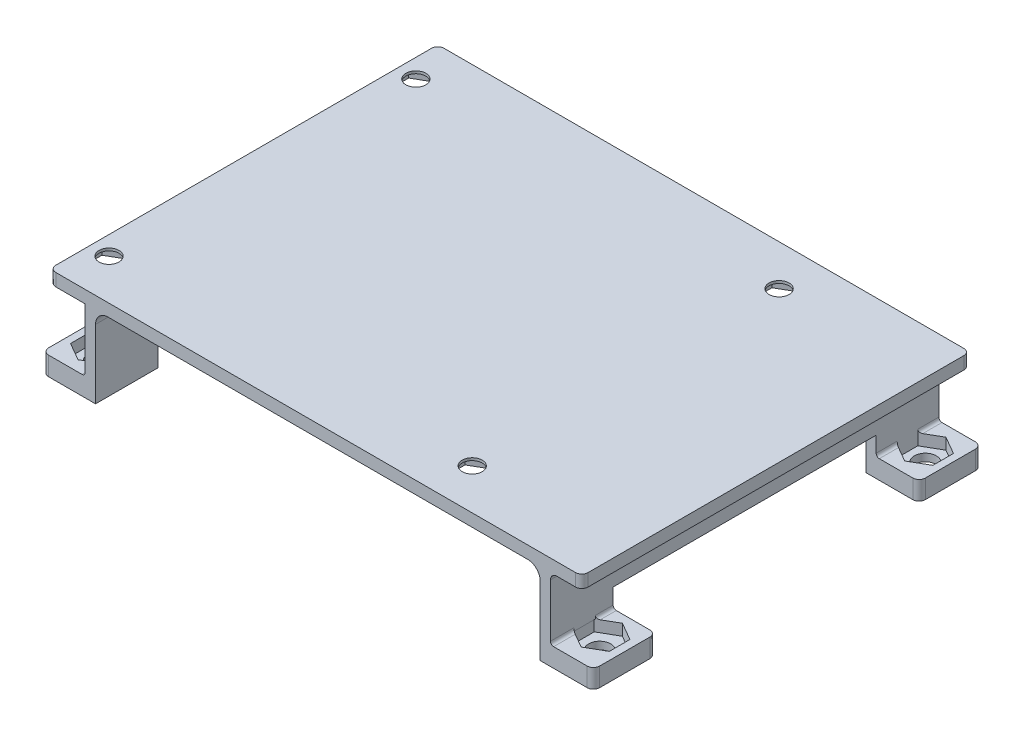
SolidWorks part; units mm, degrees
ref_plane "前基準面" through (0, 0, 0) normal (0, 0, 1) x (1, 0, 0)
ref_plane "上基準面" through (0, 0, 0) normal (0, 1, 0) x (1, 0, 0)
ref_plane "右基準面" through (0, 0, 0) normal (1, 0, 0) x (0, 0, -1)
sketch "草圖1" plane through (0, 0, 0) normal (0, 0, 1) x (1, 0, 0)
  line L0 (-133.4262, 0) -> (6537.8852, 0) construction
  line L1 (0, -133.4262) -> (0, 6537.8852) construction
  line L2 (-44, 0) -> (-44, 3)
  line L3 (-44, 3) -> (-37.15, 3)
  line L4 (-37.15, 3) -> (-37.15, 13)
  line L6 (37.15, 13) -> (37.15, 3)
  line L7 (37.15, 3) -> (44, 3)
  line L8 (44, 3) -> (44, 0)
  line L10 (-35.5, 0) -> (-35.5, 13)
  line L11 (-35.5, 13) -> (35.5, 13)
  line L12 (35.5, 13) -> (35.5, 0)
  line L13 (-44, 0) -> (-35.5, 0)
  line L14 (35.5, 0) -> (44, 0)
  line L16 (-42.85, 15) -> (-42.85, 13)
  line L17 (-37.15, 13) -> (-42.85, 13)
  line L18 (-42.85, 15) -> (42.15, 15)
  line L19 (42.15, 15) -> (42.15, 13)
  line L20 (42.15, 13) -> (37.15, 13)
  dimension "D1" = 1.65
  dimension "D2" = 13
  dimension "D3" = 71
  dimension "D4" = 88
  dimension "D5" = 2
  dimension "D6" = 3
  dimension "D7" = 85
  dimension "D8" = 5.7
extrude "填料-伸長1" add sketch "草圖1" along normal mid plane 62
sketch "草圖2" plane through (0, 0, 0) normal (1, 0, 0) x (0, 0, -1)
  line L0 (-1000, 0) -> (49000, 0) construction
  line L1 (0, -1000) -> (0, 49000) construction
  line L3 (-21, -6) -> (21, -6)
  line L4 (-21, -6) -> (-21, 6)
  line L5 (-21, 6) -> (21, 6)
  line L6 (21, -6) -> (21, 6)
  line L7 (-21, -6) -> (21, 6) construction
  line L8 (-21, 6) -> (21, -6) construction
  point P4 (0, 0)
  dimension "D1" = 42
  dimension "D2" = 12
extrude "除料-伸長1" cut sketch "草圖2" against normal through all both and the other way through all
sketch "草圖3" plane through (0, 0, 0) normal (0, 1, 0) x (1, 0, 0)
  line L0 (-40, -1017.5) -> (-40, 48982.5) construction
  line L2 (40, -1017.5) -> (40, 48982.5) construction
  line L4 (-1031.5, 26) -> (48968.5, 26) construction
  line L5 (0, -1000) -> (0, 49000) construction
  line L6 (-1031.5, -26) -> (48968.5, -26) construction
  line L8 (-1000, 0) -> (49000, 0) construction
  line L9 (-42.85, -31) -> (-37.15, -31) construction
  line L10 (35.5, -31) -> (44, -31) construction
  circle A0 centre (-40, 26) radius 1.75
  circle A1 centre (40, 26) radius 1.75
  circle A2 centre (40, -26) radius 1.75
  circle A3 centre (-40, -26) radius 1.75
  point P12 (-40, -31)
  point P16 (40, -31)
  dimension "D1" = 3.5
  dimension "D2" = 52
  dimension "D3" = 80
extrude "除料-伸長3" cut sketch "草圖3" along normal up to next
sketch "草圖5" plane through (0, 15, 0) normal (0, 1, 0) x (1, 0, 0)
  line L0 (-1000, 0) -> (49000, 0) construction
  line L1 (-1033.1907, 24.5) -> (48966.8093, 24.5) construction
  line L2 (-1033.1907, -24.5) -> (48966.8093, -24.5) construction
  line L3 (-39.85, 24.5) -> (-39.85, -24.5) construction
  line L4 (18.15, 24.5) -> (18.15, -24.5) construction
  line L5 (-42.85, -31) -> (-42.85, 31) construction
  circle A0 centre (-39.85, 24.5) radius 1.6
  circle A1 centre (-39.85, -24.5) radius 1.6
  circle A2 centre (18.15, 24.5) radius 1.6
  circle A3 centre (18.15, -24.5) radius 1.6
  dimension "D3" = 3.2
  dimension "D1" = 49
  dimension "D2" = 24.5
  dimension "D4" = 58
  dimension "D5" = 3
extrude "除料-伸長5" cut sketch "草圖5" against normal blind 5
ref_plane "平面1" through (0, 3, 0) normal (0, 1, 0) x (1, 0, 0)
sketch "草圖17" plane through (0, 13, 0) normal (0, -1, 0) x (1, 0, 0)
  line L7 (20.85, 22.9412) -> (20.85, 26.0588)
  line L8 (20.85, 26.0588) -> (18.15, 27.6177)
  line L9 (18.15, 27.6177) -> (15.45, 26.0588)
  line L10 (15.45, 26.0588) -> (15.45, 22.9412)
  line L11 (15.45, 22.9412) -> (18.15, 21.3823)
  line L12 (18.15, 21.3823) -> (20.85, 22.9412)
  line L13 (20.85, -26.0588) -> (20.85, -22.9412)
  line L14 (20.85, -22.9412) -> (18.15, -21.3823)
  line L15 (18.15, -21.3823) -> (15.45, -22.9412)
  line L16 (15.45, -22.9412) -> (15.45, -26.0588)
  line L17 (15.45, -26.0588) -> (18.15, -27.6177)
  line L18 (18.15, -27.6177) -> (20.85, -26.0588)
  line L19 (-39.85, 21.3823) -> (-37.15, 22.9412)
  line L20 (-37.15, 22.9412) -> (-37.15, 26.0588)
  line L21 (-37.15, 26.0588) -> (-39.85, 27.6177)
  line L22 (-39.85, 27.6177) -> (-42.55, 26.0588)
  line L23 (-42.55, 26.0588) -> (-42.55, 22.9412)
  line L24 (-42.55, 22.9412) -> (-39.85, 21.3823)
  line L26 (-39.85, -27.6177) -> (-37.15, -26.0588)
  line L27 (-37.15, -26.0588) -> (-37.15, -22.9412)
  line L28 (-37.15, -22.9412) -> (-39.85, -21.3823)
  line L29 (-39.85, -21.3823) -> (-42.55, -22.9412)
  line L30 (-42.55, -22.9412) -> (-42.55, -26.0588)
  line L31 (-42.55, -26.0588) -> (-39.85, -27.6177)
  circle A0 centre (18.15, 24.5) radius 2.7 construction
  circle A1 centre (18.15, -24.5) radius 2.7 construction
  circle A2 centre (-39.85, 24.5) radius 2.7 construction
  circle A3 centre (-39.85, -24.5) radius 2.7 construction
  dimension "D1" = 5.4
  dimension "D2" = 5.4
  dimension "D3" = 5.4
  dimension "D4" = 5.4
extrude "除料-伸長8" cut sketch "草圖17" against normal blind 1.6
fillet "圓角1" radius 1 12 edges at (42.15, 14, -31) (44, 1.5, -31) (44, 1.5, -21) (44, 1.5, 21) (44, 1.5, 31) (42.15, 14, 31) (-42.85, 14, -31) (-44, 1.5, -31) (-44, 1.5, -21) (-44, 1.5, 21) (-44, 1.5, 31) (-42.85, 14, 31)
fillet "圓角7" radius 2 2 edges at (35.5, 13, 0) (-35.5, 13, 0)
sketch "草圖19" plane through (0, 3, 0) normal (0, 1, 0) x (1, 0, 0)
  line L1 (-40, -29.2909) -> (-37.15, -27.6454)
  line L2 (-37.15, -27.6454) -> (-37.15, -24.3546)
  line L3 (-37.15, -24.3546) -> (-40, -22.7091)
  line L4 (-40, -22.7091) -> (-42.85, -24.3546)
  line L5 (-42.85, -24.3546) -> (-42.85, -27.6454)
  line L6 (-42.85, -27.6454) -> (-40, -29.2909)
  line L7 (39.8961, -28.8509) -> (42.7461, -27.2055)
  line L8 (42.7461, -27.2055) -> (42.7461, -23.9146)
  line L9 (42.7461, -23.9146) -> (39.8961, -22.2691)
  line L10 (39.8961, -22.2691) -> (37.0461, -23.9146)
  line L11 (37.0461, -23.9146) -> (37.0461, -27.2055)
  line L12 (37.0461, -27.2055) -> (39.8961, -28.8509)
  line L13 (42.85, 24.3546) -> (42.85, 27.6454)
  line L14 (42.85, 27.6454) -> (40, 29.2909)
  line L15 (40, 29.2909) -> (37.15, 27.6454)
  line L16 (37.15, 27.6454) -> (37.15, 24.3546)
  line L17 (37.15, 24.3546) -> (40, 22.7091)
  line L18 (40, 22.7091) -> (42.85, 24.3546)
  line L19 (-40, 22.7091) -> (-37.15, 24.3546)
  line L20 (-37.15, 24.3546) -> (-37.15, 27.6454)
  line L21 (-37.15, 27.6454) -> (-40, 29.2909)
  line L22 (-40, 29.2909) -> (-42.85, 27.6454)
  line L23 (-42.85, 27.6454) -> (-42.85, 24.3546)
  line L24 (-42.85, 24.3546) -> (-40, 22.7091)
  circle A0 centre (-40, -26) radius 2.85 construction
  circle A1 centre (39.8961, -25.56) radius 2.85 construction
  circle A2 centre (40, 26) radius 2.85 construction
  circle A3 centre (-40, 26) radius 2.85 construction
  dimension "D1" = 5.7
  dimension "D2" = 5.7
  dimension "D3" = 5.7
  dimension "D4" = 5.7
extrude "除料-伸長9" cut sketch "草圖19" against normal blind 1.8
fillet "圓角5" radius 0.5 8 edges at (37.15, 3, -22.6773) (37.15, 3, -29.3227) (37.15, 3, 29.1327) (37.15, 3, 22.4273) (-37.15, 3, -22.6773) (-37.15, 3, -29.3227) (-37.15, 3, 22.6773) (-37.15, 3, 29.3227)
fillet "圓角8" radius 1 1 edges at (37.15, 13, 0)
